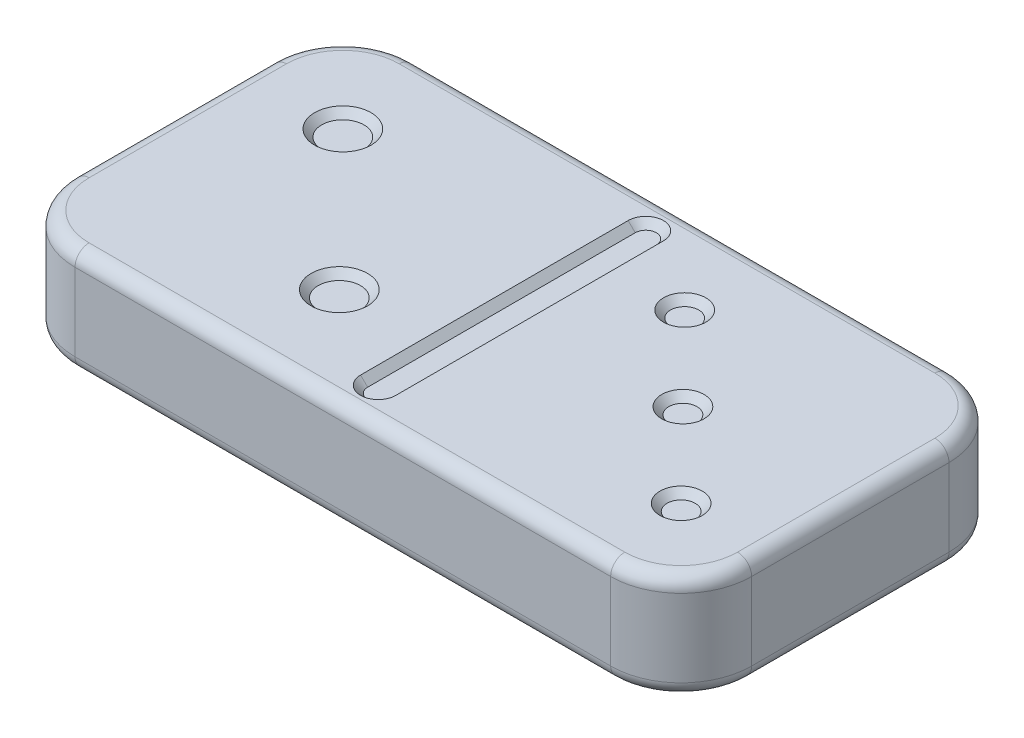
SolidWorks part; units mm, degrees
material "ABS"
ref_plane "Front Plane" through (0, 0, 0) normal (0, 0, 1) x (1, 0, 0)
ref_plane "Top Plane" through (0, 0, 0) normal (0, 1, 0) x (1, 0, 0)
ref_plane "Right Plane" through (0, 0, 0) normal (1, 0, 0) x (0, 0, -1)
sketch "Esquisse1" plane through (0, 0, 0) normal (0, 1, 0) x (1, 0, 0)
  line L1 (0, 0) -> (48, 0)
  line L2 (0, 0) -> (0, 24)
  line L3 (0, 24) -> (48, 24)
  line L4 (48, 0) -> (48, 24)
  dimension "D1" = 48
  dimension "D2" = 24
extrude "Extrusion1" add sketch "Esquisse1" along normal blind 7.5
fillet "Congé2" radius 5 4 edges at (48, 3.75, 0) (48, 3.75, -24) (0, 3.75, 0) (0, 3.75, -24)
fillet "Congé5" radius 1 8 edges at (46.5355, 7.5, -22.5355) (48, 7.5, -12) (46.5355, 7.5, -1.4645) (24, 7.5, 0) (1.4645, 7.5, -1.4645) (0, 7.5, -12) (1.4645, 7.5, -22.5355) (24, 7.5, -24)
fillet "Congé6" radius 1 8 edges at (46.5355, 0, -22.5355) (48, 0, -12) (46.5355, 0, -1.4645) (24, 0, 0) (1.4645, 0, -1.4645) (0, 0, -12) (1.4645, 0, -22.5355) (24, 0, -24)
sketch "Esquisse4" plane through (0, 7.5, 0) normal (0, 1, 0) x (1, 0, 0)
  line L0 (1, 12) -> (47, 12) construction
  line L1 (1, 19) -> (1, 5) construction
  line L2 (47, 5) -> (47, 19) construction
  line L3 (24, 23) -> (24, 1) construction
  line L4 (43, 23) -> (5, 23) construction
  line L5 (5, 1) -> (43, 1) construction
  line L7 (23.75, 21.4914) -> (24.25, 21.4914)
  line L8 (23.75, 21.4914) -> (23.75, 2.5086)
  line L9 (23.75, 2.5086) -> (24.25, 2.5086)
  line L10 (24.25, 21.4914) -> (24.25, 2.5086)
  line L11 (23.75, 21.4914) -> (24.25, 2.5086) construction
  line L12 (23.75, 2.5086) -> (24.25, 21.4914) construction
  point P12 (24, 12)
  dimension "D1" = 0.5
extrude "Extrusion2" cut sketch "Esquisse4" against normal blind 0.5
sketch "Esquisse5" plane through (0, 7.5, 0) normal (0, 1, 0) x (1, 0, 0)
  line L0 (24.25, 21.4914) -> (23.75, 21.4914) construction
  line L1 (23.75, 2.5086) -> (24.25, 2.5086) construction
  circle A0 centre (24, 21.4914) radius 0.25
  circle A1 centre (24, 2.5086) radius 0.25
  dimension "D1" = 0.5
  dimension "D2" = 0.5
extrude "Extrusion3" cut sketch "Esquisse5" against normal blind 0.5
chamfer "Chanfrein1" distance 1 angle 45 4 edges at (24, 7.5, -21.7414) (24.25, 7.5, -12) (24, 7.5, -2.2586) (23.75, 7.5, -12)
sketch "Esquisse9" plane through (0, 7.5, 0) normal (0, 1, 0) x (1, 0, 0)
  line L0 (43, 23) -> (5, 23) construction
  line L1 (25.25, 21.4914) -> (25.25, 2.5086) construction
  line L2 (47, 5) -> (47, 19) construction
  line L3 (5, 1) -> (43, 1) construction
  line L4 (30.25, 18) -> (42, 6) construction
  circle A0 centre (30.25, 18) radius 1.5
  circle A1 centre (36.125, 12) radius 1.5
  circle A2 centre (42, 6) radius 1.5
  dimension "D1" = 3
  dimension "D2" = 3
  dimension "D3" = 3
  dimension "D4" = 5
  dimension "D5" = 5
  dimension "D6" = 5
  dimension "D7" = 5
extrude "Extrusion6" cut sketch "Esquisse9" against normal blind 0.5 draft 45
sketch "Esquisse10" plane through (0, 7.5, 0) normal (0, 1, 0) x (1, 0, 0)
  line L0 (1, 19) -> (1, 5) construction
  line L1 (22.75, 2.5086) -> (22.75, 21.4914) construction
  line L2 (43, 23) -> (5, 23) construction
  line L3 (5, 1) -> (43, 1) construction
  circle A0 centre (7, 17) radius 2
  circle A1 centre (16.75, 7) radius 2
  dimension "D1" = 4
  dimension "D2" = 4
  dimension "D3" = 6
  dimension "D4" = 6
  dimension "D5" = 6
  dimension "D6" = 6
extrude "Extrusion7" cut sketch "Esquisse10" against normal blind 0.5 draft 45
